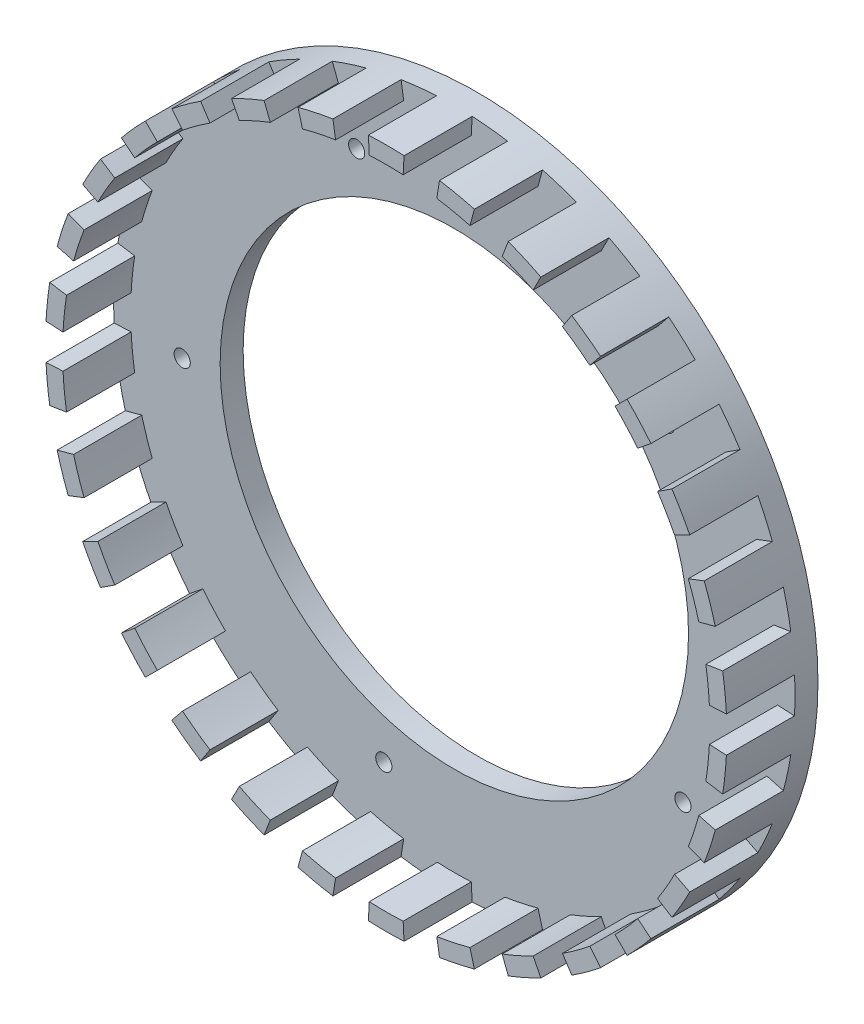
SolidWorks part; units mm, degrees
ref_plane "Front Plane" through (0, 0, 0) normal (0, 0, 1) x (1, 0, 0)
ref_plane "Top Plane" through (0, 0, 0) normal (0, 1, 0) x (1, 0, 0)
ref_plane "Right Plane" through (0, 0, 0) normal (1, 0, 0) x (0, 0, -1)
ref_axis "X-Axis" through (-88.99, 0, 0) along (1, 0, 0)
ref_axis "Y-Axis" through (0, 55, 0) along (0, -1, 0)
ref_axis "Z-Axis" through (0, 0, -88.99) along (0, 0, 1)
sketch "Sketch1" plane through (0, 0, 0) normal (0, 0, 1) x (1, 0, 0)
  circle A0 centre (0, 0) radius 40
  dimension "D1" = 80
extrude "Boss-Extrude1" add sketch "Sketch1" along normal blind 3
sketch "Sketch2" plane through (0, 0, 3) normal (0, 0, 1) x (1, 0, 0)
  circle A0 centre (0, 0) radius 27.5
  dimension "D1" = 55
extrude "Cut-Extrude1" cut sketch "Sketch2" against normal through all
other "Move Face1" flip direction yes face at (27.5, 0, 0) offset 0.3 parameters "D1"=0.3
sketch "Sketch6" plane through (0, 0, 0.3) normal (0, 0, -1) x (-1, 0, 0)
  line L0 (0, 0) -> (0, 40) construction
  line L1 (0, 0) -> (11.4678, 29.8746) construction
  circle A0 centre (0, 0) radius 40 construction
  circle A1 centre (11.4678, 29.8746) radius 0.95
  dimension "D2" = 1.9
  dimension "D1" = 32
  dimension "D3" = 21
extrude "Cut-Extrude8" cut sketch "Sketch6" against normal through all
pattern_circular "CirPattern3" count 5 over 360 about axis through (0, 0, -88.99) along (0, 0, 1) of "Cut-Extrude8"
sketch "Sketch7" plane through (0, 0, 3) normal (0, 0, 1) x (1, 0, 0)
  line L0 (-1.9888, 37.9479) -> (-2.0934, 39.9452)
  line L1 (1.9888, 37.9479) -> (2.0934, 39.9452)
  line L2 (0, 0) -> (0, 40) construction
  line L3 (-1.9888, 37.9479) -> (0, 0) construction
  line L4 (0, 0) -> (1.9888, 37.9479) construction
  arc A0 (1.9888, 37.9479) -> (-1.9888, 37.9479) centre (0, 0) ccw
  arc A1 (2.0934, 39.9452) -> (-2.0934, 39.9452) centre (0, 0) ccw
  circle A2 centre (0, 0) radius 40 construction
  point P1 (0, 45)
  dimension "D1" = 2
  dimension "D3" = 3
  dimension "D4" = 3
extrude "Boss-Extrude2" add sketch "Sketch7" along normal blind 8
pattern_circular "CirPattern4" count 30 every 12 about axis through (0, 0, -88.99) along (0, 0, 1) of "Boss-Extrude2"
